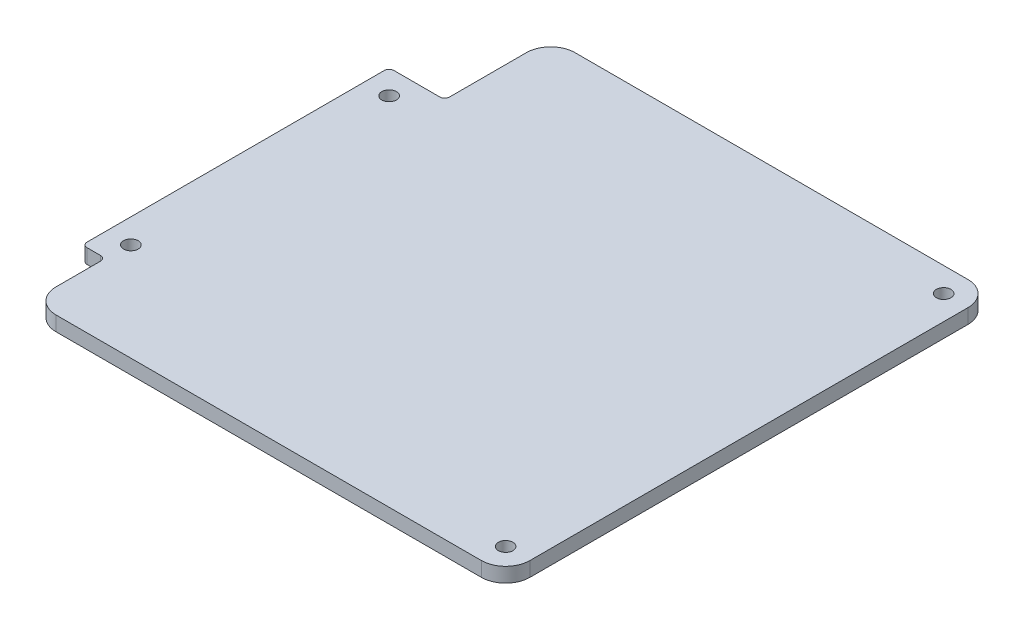
SolidWorks part; units mm, degrees
ref_plane "Front Plane" through (0, 0, 0) normal (0, 0, 1) x (1, 0, 0)
ref_plane "Top Plane" through (0, 0, 0) normal (0, 1, 0) x (1, 0, 0)
ref_plane "Right Plane" through (0, 0, 0) normal (1, 0, 0) x (0, 0, -1)
ref_plane "Plane1" through (0, 23, 0) normal (0, 1, 0) x (1, 0, 0)
sketch "Sketch1" plane through (0, 23, 0) normal (0, 1, 0) x (1, 0, 0)
  line L0 (98.3054, 50) -> (98.3054, 28.2195)
  line L1 (189.0458, 50) -> (98.3054, 50)
  line L2 (189.0458, 50) -> (189.0458, -50)
  line L3 (189.0458, -50) -> (97.6502, -50)
  line L5 (98.3054, 28.2195) -> (86.88, 28.2195)
  line L6 (86.88, 28.2195) -> (86.88, -34.8422)
  line L7 (86.88, -34.8422) -> (91.6598, -34.8422)
  line L8 (91.6598, -34.8422) -> (91.6598, -50)
  line L9 (91.6598, -50) -> (97.6502, -50)
  line L10 (94.8054, 33.2195) -> (98.3054, 33.2195) construction
  line L11 (184.0458, 45) -> (184.0458, 50) construction
  line L12 (93.3054, 31.7195) -> (93.3054, 28.2195) construction
  line L13 (99.4745, -34.8422) -> (86.1225, -34.8422) construction
  line L14 (88.1598, -39.8422) -> (91.6598, -39.8422) construction
  line L15 (86.6598, -38.3422) -> (86.6598, -34.8422) construction
  line L16 (189.0458, 0) -> (190, 0) construction
  line L17 (190, -60) -> (190, 60) construction
  line L18 (105.0183, -40) -> (185.0183, -40) construction
  line L19 (105.0183, -40) -> (105.0183, 40) construction
  line L20 (105.0183, 40) -> (185.0183, 40) construction
  line L21 (185.0183, -40) -> (185.0183, 40) construction
  line L22 (184.0458, 45) -> (189.0458, 45) construction
  line L23 (184.0458, -45) -> (189.0458, -45) construction
  line L24 (184.0458, -45) -> (184.0458, -50) construction
  line L25 (91.88, 23.2195) -> (91.88, 28.2195) construction
  line L26 (91.88, 23.2195) -> (86.88, 23.2195) construction
  line L27 (91.88, -29.8422) -> (91.88, -34.8422) construction
  line L28 (91.88, -29.8422) -> (86.88, -29.8422) construction
  circle A0 centre (86.6598, -39.8422) radius 1.5 construction
  circle A1 centre (93.3054, 33.2195) radius 1.5 construction
  circle A2 centre (184.0458, 45) radius 1.5 construction
  circle A3 centre (184.0458, 45) radius 1.5 construction
  circle A4 centre (184.0458, -45) radius 1.5 construction
  circle A6 centre (91.88, 23.2195) radius 1.5 construction
  circle A7 centre (91.88, -29.8422) radius 1.5 construction
  point P32 (185.0183, 0)
  point P39 (99.4745, -34.8422)
  dimension "D1" = 100
  dimension "D2" = 80
  dimension "D3" = 3.5
  dimension "D4" = 5
extrude "Boss-Extrude1" add sketch "Sketch1" along normal blind 3
fillet "Fillet3" radius 5 4 edges at (189.0458, 24.5, -50) (98.3054, 24.5, -50) (91.6598, 24.5, 50) (189.0458, 24.5, 50)
fillet "Fillet2" radius 1 4 edges at (86.88, 24.5, -28.2195) (98.3054, 24.5, -28.2195) (91.6598, 24.5, 34.8422) (86.88, 24.5, 34.8422)
sketch "Sketch2" plane through (0, 23, 0) normal (0, 1, 0) x (1, 0, 0)
  circle A0 centre (184.0458, -45) radius 1.5 construction
  circle A1 centre (184.0458, -45) radius 1.5
  circle A2 centre (91.88, -29.8422) radius 1.5 construction
  circle A3 centre (91.88, -29.8422) radius 1.5
  circle A4 centre (91.88, 23.2195) radius 1.5 construction
  circle A5 centre (91.88, 23.2195) radius 1.5
  circle A6 centre (184.0458, 45) radius 1.5 construction
  circle A7 centre (184.0458, 45) radius 1.5
extrude "Cut-Extrude1" cut sketch "Sketch2" along normal up to surface (3 mm away) up to face at (116.4727, 26, 1.6557)
